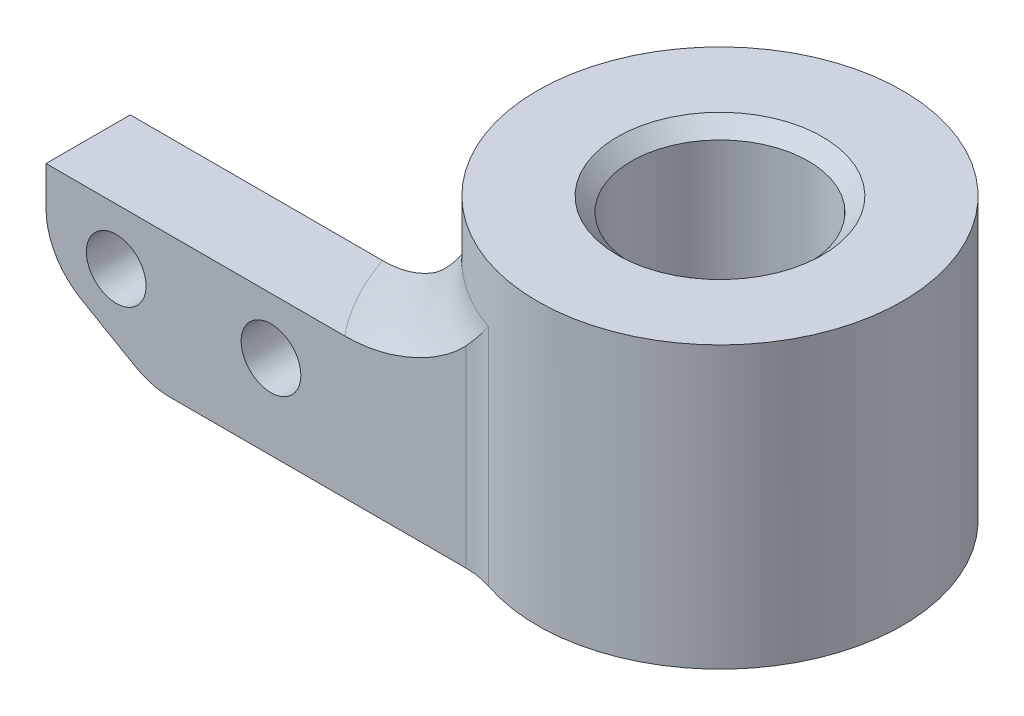
SolidWorks part; units mm, degrees
ref_plane "Front Plane" through (0, 0, 0) normal (0, 0, 1) x (1, 0, 0)
ref_plane "Top Plane" through (0, 0, 0) normal (0, 1, 0) x (1, 0, 0)
ref_plane "Right Plane" through (0, 0, 0) normal (1, 0, 0) x (0, 0, -1)
sketch "Sketch1" plane through (0, 0, 0) normal (0, 1, 0) x (1, 0, 0)
  circle A1 centre (0, 0) radius 8.255
  dimension "D2" = 16.51
extrude "Boss-Extrude1" add sketch "Sketch1" along normal mid plane 12.7
sketch "Sketch2" plane through (0, 0, 0) normal (0, 0, 1) x (1, 0, 0)
  line L0 (-8.255, -6.35) -> (8.255, -6.35) construction
  line L1 (-22.86, 0) -> (0, 0)
  line L2 (-22.86, 0) -> (-22.86, -6.35)
  line L3 (-22.86, -6.35) -> (0, -6.35)
  line L4 (0, 0) -> (0, -6.35)
  line L5 (-22.86, 0) -> (0, -6.35) construction
  line L6 (-22.86, -6.35) -> (0, 0) construction
  point P0 (-11.43, -3.175)
  point P7 (0, 0)
  dimension "D1" = 22.86
  dimension "D3" = 6.35
extrude "Boss-Extrude2" add sketch "Sketch2" along normal blind 3.81 from offset 3.81
hole_wizard "M7 Clearance Hole2" positions "Sketch5" profile "Sketch6" hole size "M7" standard "ANSI Metric" end condition through all
sketch "Sketch5" plane through (0, 6.35, 0) normal (0, 1, 0) x (1, 0, 0)
  point P0 (0, 0)
sketch "Sketch6" plane through (0, 6.35, 0) normal (1, 0, 0) x (0, 0, 1)
  line L0 (0, 0) -> (0, 12.7)
  line L1 (0, 12.7) -> (4, 12.7)
  line L2 (4, 12.7) -> (4, 0)
  line L5 (4, 0) -> (0, 0)
  line L11 (0, -6.35) -> (0, 107.95) construction
  dimension "Thru Hole Dia." = 8
  dimension "Thru Hole Depth" = 12.7
fillet "Fillet1" radius 3.81 2 edges at (-3.175, -3.175, 7.62) (-5.5841, 0, 6.0797)
hole_wizard "M2.5 Clearance Hole1" positions "Sketch3" profile "Sketch4" hole size "M2.5" standard "ANSI Metric" end condition through all
sketch "Sketch3" plane through (0, 0, 7.62) normal (0, 0, 1) x (1, 0, 0)
  line L0 (-22.86, 0) -> (-22.86, -6.35) construction
  line L2 (-9.3541, 0) -> (-22.86, 0) construction
  point P0 (-19.685, -2.54)
  point P2 (-12.685, -2.54)
  point P5 (0, 0)
  point P9 (0, 0)
  point P10 (-22.225, -3.967)
  point P13 (-22.225, -2.5658)
  dimension "D1" = 7
  dimension "D2" = 3.175
  dimension "D3" = 2.54
sketch "Sketch4" plane through (-19.685, -2.54, 7.62) normal (1, 0, 0) x (0, -1, 0)
  line L0 (0, 0) -> (0, 15.875)
  line L1 (0, 15.875) -> (1.35, 15.875)
  line L2 (1.35, 15.875) -> (1.35, 0)
  line L5 (1.35, 0) -> (0, 0)
  line L11 (0, -6.35) -> (0, 107.95) construction
  dimension "Thru Hole Dia." = 2.7
  dimension "Thru Hole Depth" = 15.875
chamfer "Chamfer1" distance 4.7625 angle 30 1 edges at (-22.86, -6.35, 5.715) first distance on face at (0, -6.35, 4)
fillet "Fillet2" radius 3.175 2 edges at (-18.0975, -6.35, 5.715) (-22.86, -3.6004, 5.715)
fillet "Fillet3" radius 1.27 1 edges at (-7.3232, -1.27, 3.81)
chamfer "Chamfer2" distance 0.635 angle 45 2 edges at (0, -6.35, 4) (0, 6.35, 4)
